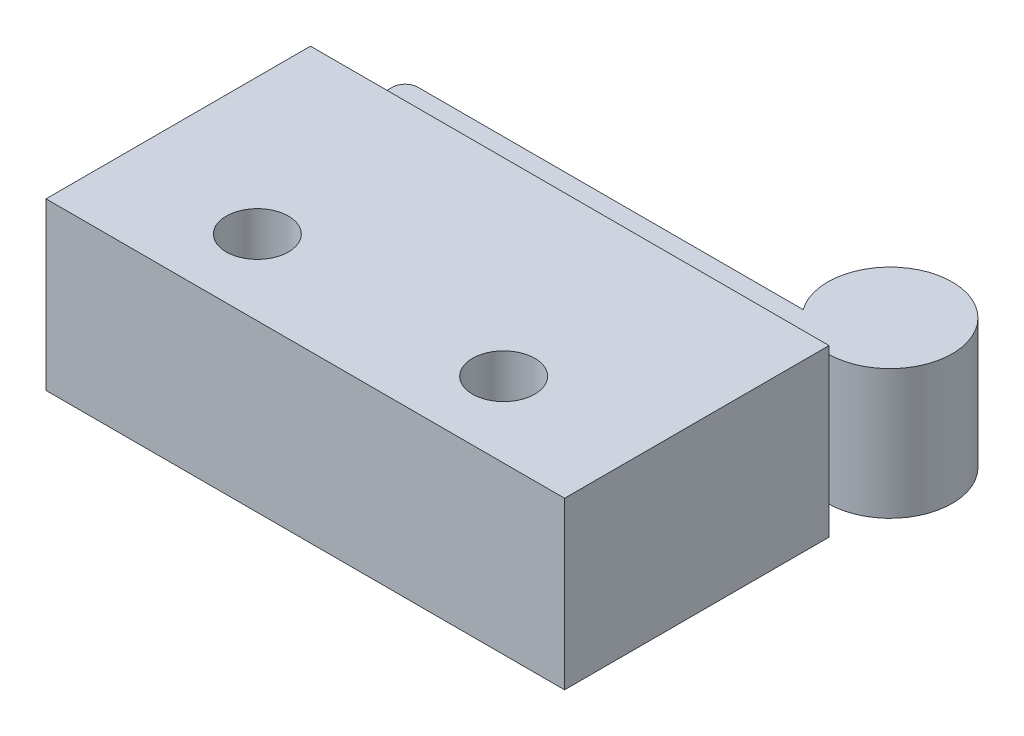
SolidWorks part; units mm, degrees
ref_plane "Front Plane" through (0, 0, 0) normal (0, 0, 1) x (1, 0, 0)
ref_plane "Top Plane" through (0, 0, 0) normal (0, 1, 0) x (1, 0, 0)
ref_plane "Right Plane" through (0, 0, 0) normal (1, 0, 0) x (0, 0, -1)
sketch "Sketch1" plane through (0, 0, 0) normal (0, 1, 0) x (1, 0, 0)
  line L0 (-4.75, -2.2) -> (4.75, -2.2) construction
  line L1 (-10, -5.1) -> (10, -5.1)
  line L2 (-10, -5.1) -> (-10, 5.1)
  line L3 (-10, 5.1) -> (10, 5.1)
  line L4 (10, -5.1) -> (10, 5.1)
  line L5 (-10, -5.1) -> (10, 5.1) construction
  line L6 (-10, 5.1) -> (10, -5.1) construction
  circle A0 centre (-4.75, -2.2) radius 1.2
  circle A1 centre (4.75, -2.2) radius 1.2
  point P0 (0, 0)
  point P8 (0, -2.2)
  point P9 (-4.75, -2.2)
  point P10 (4.75, -2.2)
  point P11 (0, -5.1)
  dimension "D5" = 2.4
  dimension "D1" = 20
  dimension "D2" = 10.2
  dimension "D3" = 9.5
  dimension "D4" = 2.9
extrude "Boss-Extrude1" add sketch "Sketch1" along normal blind 6.4
ref_plane "Plane1" through (0, 3.2, 0) normal (0, 1, 0) x (1, 0, 0)
sketch "Sketch4" plane through (0, 3.2, 0) normal (0, 1, 0) x (1, 0, 0)
  line L0 (-6.75, 5.1) -> (-6.75, 5.5)
  line L1 (10, 5.1) -> (-10, 5.1) construction
  line L2 (-6.75, 5.5) -> (9.55, 5.5)
  line L3 (7.6006, 6.5) -> (-7.75, 6.5)
  line L4 (-7.75, 6.5) -> (-7.75, 5.1)
  line L5 (-7.75, 5.1) -> (-6.75, 5.1)
  arc A0 (9.55, 5.5) -> (7.6006, 6.5) centre (9.55, 7.9) ccw
  circle A1 centre (-4.75, -2.2) radius 1.2 construction
  point P8 (9.55, 10.3)
  dimension "D1" = 4.8
  dimension "D2" = 14.3
  dimension "D3" = 1
  dimension "D4" = 1
  dimension "D5" = 2
  dimension "D6" = 5.2
extrude "Boss-Extrude2" add sketch "Sketch4" along normal mid plane 5
sketch "Sketch5" [suppressed] plane through (0, 5.7, 0) normal (0, 1, 0) x (1, 0, 0)
  line L0 (7.6006, 6.5) -> (9.55, 6.5)
  line L1 (9.55, 6.5) -> (9.55, 5.5)
  line L8 (-7.75, 5.1) -> (-6.75, 5.1)
  line L9 (-6.75, 5.1) -> (-6.75, 5.5)
  line L10 (-6.75, 5.5) -> (9.55, 5.5)
  line L11 (7.6006, 6.5) -> (-7.75, 6.5)
  line L12 (-7.75, 6.5) -> (-7.75, 5.1)
  arc A2 (9.55, 5.5) -> (7.6006, 6.5) centre (9.55, 7.9) ccw
  arc A3 (9.55, 5.5) -> (7.6006, 6.5) centre (9.55, 7.9) ccw
  dimension "D1" = 0
extrude "Cut-Extrude1" [suppressed] cut sketch "Sketch5" against normal through all
sketch "Sketch6" [suppressed] plane through (0, 5.7, 0) normal (0, 1, 0) x (1, 0, 0)
  line L0 (-6.75, 5.5) -> (9.55, 5.5) construction
  line L1 (9.55, 6.5) -> (43.15, 6.5)
  line L2 (9.55, 6.5) -> (9.55, 5.5)
  line L3 (9.55, 5.5) -> (43.15, 5.5)
  line L4 (43.15, 6.5) -> (43.15, 5.5)
  circle A0 centre (-4.75, -2.2) radius 1.2 construction
  dimension "D1" = 47.9
extrude "Boss-Extrude3" [suppressed] add sketch "Sketch6" against normal up to surface (5 mm away)
fillet "Fillet1" radius 0.5 2 edges at (-6.75, 3.2, -5.5) (-7.75, 3.2, -6.5)
